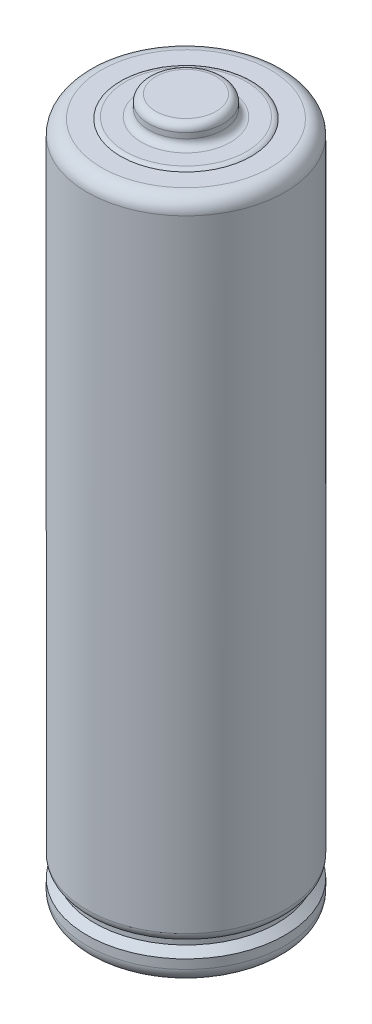
SolidWorks part; units mm, degrees
ref_plane "Front Plane" through (0, 0, 0) normal (0, 0, 1) x (1, 0, 0)
ref_plane "Top Plane" through (0, 0, 0) normal (0, 1, 0) x (1, 0, 0)
ref_plane "Right Plane" through (0, 0, 0) normal (1, 0, 0) x (0, 0, -1)
sketch "Sketch1" plane through (0, 0, 0) normal (0, 1, 0) x (1, 0, 0)
  circle A0 centre (0, 0) radius 7.0231
  dimension "D1" = 14.0462
extrude "Boss-Extrude1" add sketch "Sketch1" along normal blind 48.387
fillet "Fillet1" radius 1.016 2 edges at (0, 0, 7.0231) (0, 48.387, 7.0231)
sketch "Sketch3" plane through (0, 48.387, 0) normal (0, 1, 0) x (1, 0, 0)
  circle A0 centre (0, 0) radius 4.6355
  dimension "D1" = 9.271
extrude "Boss-Extrude2" add sketch "Sketch3" along normal blind 0.127
fillet "Fillet2" radius 0.508 1 edges at (0, 48.514, 4.6355)
sketch "Sketch4" plane through (0, 48.514, 0) normal (0, 1, 0) x (1, 0, 0)
  circle A0 centre (0, 0) radius 2.6479
  dimension "D1" = 5.2959
extrude "Boss-Extrude3" add sketch "Sketch4" along normal blind 1.397
fillet "Fillet3" radius 0.508 2 edges at (0, 49.911, 2.6479) (0, 48.514, 2.6479)
sketch "Sketch5" plane through (0, 0, 0) normal (1, 0, 0) x (0, 0, -1)
  line L0 (6.4834, 2.5413) -> (6.4834, 2.1382)
  line L1 (6.4834, 2.1382) -> (7.0231, 1.6637)
  line L2 (7.0231, 1.6637) -> (7.0231, 3.302)
  line L3 (7.0231, 1.016) -> (7.0231, 47.371) construction
  line L7 (7.0231, 3.302) -> (7.0231, 1.6637)
  line L8 (0, 0) -> (0, 51.4652) construction
  arc A0 (7.0231, 3.302) -> (6.4834, 2.5413) centre (6.275, 3.261) cw
revolve "Cut-Revolve2" cut sketch "Sketch5" angle 360 about L8 region at (0, 2.3197, -6.8079)
sketch "Sketch6" plane through (0, 0, 0) normal (0, -1, 0) x (1, 0, 0)
  circle A1 centre (0, 0) radius 5.3213
  circle A2 centre (0, 0) radius 4.4831
extrude "Cut-Extrude1" cut sketch "Sketch6" against normal blind 1.397
fillet "Fillet4" radius 0.508 1 edges at (0, 0, -5.3213)
fillet "Fillet5" radius 0.508 1 edges at (0, 1.397, -4.4831)
fillet "Fillet6" radius 1.016 1 edges at (0, 0, -4.4831)
sketch "Sketch7" plane through (0, 0, 0) normal (1, 0, 0) x (0, 0, -1)
  line L0 (-7.0231, 1.016) -> (7.0231, 1.016) construction
  line L1 (4.8083, 1.016) -> (-4.9848, 1.016)
  line L2 (4.8083, 1.016) -> (4.8083, 0.508)
  line L3 (4.8083, 0.508) -> (-4.9848, 0.508)
  line L4 (-4.9848, 1.016) -> (-4.9848, 0.508)
  line L5 (-5.3213, 0.508) -> (5.3213, 0.508) construction
extrude "Cut-Extrude2" cut sketch "Sketch7" against normal mid plane 0.762
